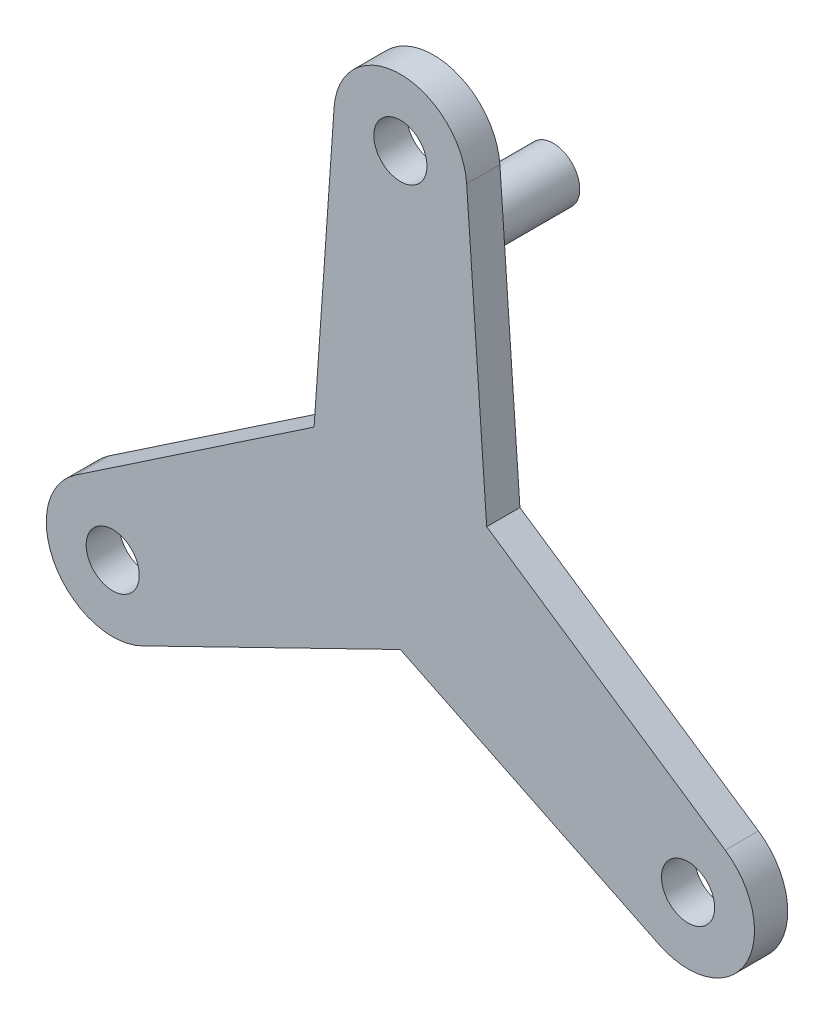
SolidWorks part; units mm, degrees
ref_plane "Front Plane" through (0, 0, 0) normal (0, 0, 1) x (1, 0, 0)
ref_plane "Top Plane" through (0, 0, 0) normal (0, 1, 0) x (1, 0, 0)
ref_plane "Right Plane" through (0, 0, 0) normal (1, 0, 0) x (0, 0, -1)
ref_axis "X" through (-88.99, 0, 0) along (1, 0, 0)
ref_axis "Y" through (0, 55, 0) along (0, -1, 0)
ref_axis "Z" through (0, 0, -88.99) along (0, 0, 1)
sketch "Sketch1" plane through (0, 0, 0) normal (0, 0, 1) x (1, 0, 0)
  line L0 (0, 0) -> (0, -50) construction
  line L1 (0, -50) -> (-43.3013, -75) construction
  line L2 (0, -50) -> (43.3013, -75) construction
  line L3 (0, -50) -> (-12.9904, -42.5) construction
  line L4 (-38.9163, -83.9873) -> (0, -65)
  line L5 (0, -65) -> (38.9163, -83.9873)
  line L6 (-12.9904, -42.5) -> (0, -50) construction
  line L7 (0, -50) -> (12.9904, -42.5) construction
  line L8 (-12.9904, -42.5) -> (-48.8921, -66.7089)
  line L9 (48.8921, -66.7089) -> (12.9904, -42.5)
  line L10 (-12.9904, -42.5) -> (-9.9757, 0.6962)
  line L11 (12.9904, -42.5) -> (9.9757, 0.6962)
  circle A0 centre (-43.3013, -75) radius 10 construction
  circle A1 centre (43.3013, -75) radius 10 construction
  circle A2 centre (0, -50) radius 15 construction
  circle A3 centre (0, 0) radius 10 construction
  arc A4 (-48.8921, -66.7089) -> (-38.9163, -83.9873) centre (-43.3013, -75) ccw
  arc A5 (48.8921, -66.7089) -> (38.9163, -83.9873) centre (43.3013, -75) cw
  arc A9 (-9.9757, 0.6962) -> (9.9757, 0.6962) centre (0, 0) cw
  point P21 (0, 10)
  dimension "D6" = 20
  dimension "D7" = 20
  dimension "D8" = 30
  dimension "D9" = 20
  dimension "D1" = 50
  dimension "D2" = 50
  dimension "D3" = 50
  dimension "D4" = 120
  dimension "D5" = 120
  dimension "D10" = 60
  dimension "D11" = 60
  dimension "D12" = 10
extrude "Boss-Extrude1" add sketch "Sketch1" along normal blind 5 contours L11 A9 L10 L8 A4 L4 L5 A5 L9
sketch "Sketch3" plane through (0, 0, 0) normal (0, 0, -1) x (-1, 0, 0)
  circle A0 centre (0, 30) radius 4
  circle A1 centre (0, 0) radius 4
  circle A2 centre (-43.3013, -75) radius 4
  circle A3 centre (43.3013, -75) radius 4
  dimension "D1" = 8
  dimension "D2" = 8
  dimension "D3" = 8
  dimension "D4" = 8
extrude "Cut-Extrude1" cut sketch "Sketch3" against normal blind 5
sketch "Sketch4" plane through (0, 0, 0) normal (0, 0, -1) x (-1, 0, 0)
  line L0 (0, -75) -> (0, 0) construction
  circle A0 centre (0, -14.5) radius 4
  dimension "D2" = 8
  dimension "D1" = 14.5
extrude "peg" add sketch "Sketch4" along normal blind 18
